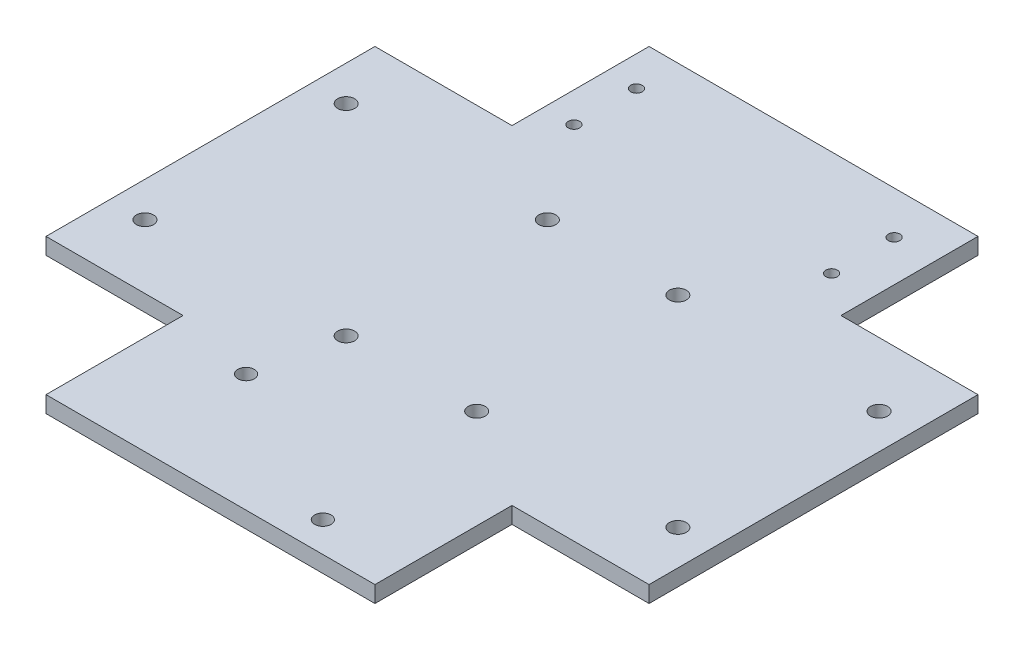
SolidWorks part; units mm, degrees
ref_plane "Front Plane" through (0, 0, 0) normal (0, 0, 1) x (1, 0, 0)
ref_plane "Top Plane" through (0, 0, 0) normal (0, 1, 0) x (1, 0, 0)
ref_plane "Right Plane" through (0, 0, 0) normal (1, 0, 0) x (0, 0, -1)
sketch "Sketch1" plane through (0, 0, 0) normal (0, 1, 0) x (1, 0, 0)
  line L0 (-55, 0) -> (55, 0) construction
  line L1 (55, -55) -> (-55, -55)
  line L2 (55, -55) -> (55, 55)
  line L3 (55, 55) -> (-55, 55)
  line L4 (-55, -55) -> (-55, 55)
  line L5 (55, -55) -> (-55, 55) construction
  line L6 (55, 55) -> (-55, -55) construction
  line L7 (-8.5, -21.75) -> (-52, -21.75)
  line L8 (-8.5, -21.75) -> (-8.5, 21.75)
  line L9 (-8.5, 21.75) -> (-52, 21.75)
  line L10 (-52, -21.75) -> (-52, 21.75)
  line L11 (-8.5, -21.75) -> (-52, 21.75) construction
  line L12 (-8.5, 21.75) -> (-52, -21.75) construction
  line L13 (0, -55) -> (0, 55) construction
  line L14 (8.5, 21.75) -> (52, 21.75)
  line L15 (52, -21.75) -> (52, 21.75)
  line L16 (8.5, -21.75) -> (52, -21.75)
  line L17 (8.5, -21.75) -> (8.5, 21.75)
  line L18 (0, 55) -> (0, -55) construction
  line L19 (-26.5, 52) -> (26.5, 52)
  line L20 (-26.5, 52) -> (-26.5, 31)
  line L21 (-26.5, 31) -> (26.5, 31)
  line L22 (26.5, 52) -> (26.5, 31)
  line L24 (-22, -31) -> (22, -31)
  line L25 (-22, -31) -> (-22, -52)
  line L26 (-22, -52) -> (22, -52)
  line L27 (22, -31) -> (22, -52)
  line L28 (-22, -31) -> (22, -52) construction
  line L29 (-22, -52) -> (22, -31) construction
  circle A0 centre (-48.6, 18.35) radius 1.55
  circle A1 centre (-11.9, 18.35) radius 1.55
  circle A2 centre (-11.9, -18.35) radius 1.55
  circle A3 centre (-48.6, -18.35) radius 1.55
  circle A4 centre (48.6, -18.35) radius 1.55
  circle A5 centre (11.9, -18.35) radius 1.55
  circle A6 centre (11.9, 18.35) radius 1.55
  circle A7 centre (48.6, 18.35) radius 1.55
  circle A8 centre (-24.5, 47.2) radius 1.05
  circle A9 centre (-24.5, 35.8) radius 1.05
  circle A10 centre (22.5, 47.2) radius 1.05
  circle A11 centre (22.5, 35.8) radius 1.05
  circle A12 centre (-15, -33.5) radius 1.5
  circle A13 centre (15, -49.5) radius 1.5
  point P0 (0, 0)
  point P6 (-30.25, 0)
  point P25 (0, 52)
  point P26 (0, -41.5)
  point P59 (-15, -33.5)
  dimension "D12" = 3.1
  dimension "D15" = 2.1
  dimension "D20" = 2.1
  dimension "D21" = 2.1
  dimension "D24" = 2.1
  dimension "D29" = 3
  dimension "D32" = 3
  dimension "D1" = 110
  dimension "D2" = 110
  dimension "D3" = 43.5
  dimension "D4" = 43.5
  dimension "D5" = 3
  dimension "D6" = 21
  dimension "D7" = 53
  dimension "D8" = 3
  dimension "D9" = 21
  dimension "D10" = 44
  dimension "D11" = 3
  dimension "D13" = 3.4
  dimension "D16" = 2
  dimension "D17" = 4.8
  dimension "D18" = 2
  dimension "D19" = 4.8
  dimension "D22" = 4.8
  dimension "D23" = 4.8
  dimension "D25" = 49
  dimension "D26" = 49
  dimension "D27" = 2.5
  dimension "D28" = 7
  dimension "D30" = 2.5
  dimension "D31" = 7
  dimension "D14" = 4
extrude "Boss-Extrude2" add sketch "Sketch1" along normal blind 3 contours L2 L1 L4 L3 | A4 | A7 | A11 | A10 | A8 | A9 | A3 | A0 | A1 | A2 | A5 | A6 | A12 | A13
sketch "Sketch3" plane through (0, 3, 0) normal (0, 1, 0) x (1, 0, 0)
  line L0 (55, 55) -> (30, 55)
  line L1 (-55, 55) -> (-30, 55)
  line L2 (-55, 55) -> (-55, 30)
  line L3 (-55, 30) -> (-30, 30)
  line L4 (-30, 55) -> (-30, 30)
  line L5 (55, 55) -> (55, 30)
  line L6 (55, 30) -> (30, 30)
  line L7 (30, 55) -> (30, 30)
  line L8 (55, -55) -> (55, -30)
  line L9 (55, -55) -> (30, -55)
  line L10 (30, -55) -> (30, -30)
  line L11 (55, -30) -> (30, -30)
  line L12 (-55, -55) -> (-30, -55)
  line L13 (-55, -55) -> (-55, -30)
  line L14 (-55, -30) -> (-30, -30)
  line L15 (-30, -55) -> (-30, -30)
  point P5 (55, 55)
  point P20 (0, 0)
  dimension "D1" = 25
  dimension "D2" = 25
  dimension "D3" = 4
extrude "Cut-Extrude1" cut sketch "Sketch3" against normal blind 3
